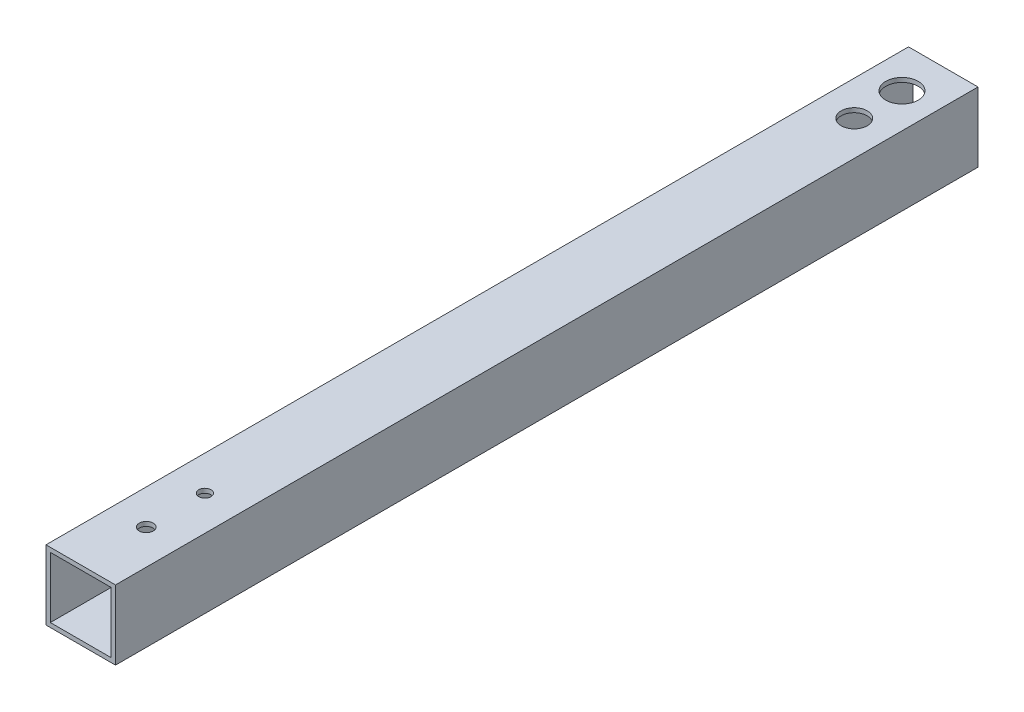
SolidWorks part; units mm, degrees
ref_plane "Front Plane" through (0, 0, 0) normal (0, 0, 1) x (1, 0, 0)
ref_plane "Top Plane" through (0, 0, 0) normal (0, 1, 0) x (1, 0, 0)
ref_plane "Right Plane" through (0, 0, 0) normal (1, 0, 0) x (0, 0, -1)
sketch "Sketch1" plane through (0, 0, 0) normal (0, 0, 1) x (1, 0, 0)
  line L1 (-8, -8) -> (8, -8)
  line L2 (-8, -8) -> (-8, 8)
  line L3 (-8, 8) -> (8, 8)
  line L4 (8, -8) -> (8, 8)
  line L5 (-8, -8) -> (8, 8) construction
  line L6 (-8, 8) -> (8, -8) construction
  line L7 (-7, -7) -> (7, -7)
  line L8 (-7, -7) -> (-7, 7)
  line L9 (-7, 7) -> (7, 7)
  line L10 (7, -7) -> (7, 7)
  line L11 (-7, -7) -> (7, 7) construction
  line L12 (-7, 7) -> (7, -7) construction
  point P0 (0, 0)
  point P6 (0, 0)
  dimension "D1" = 16
  dimension "D2" = 1
extrude "Boss-Extrude1" add sketch "Sketch1" along normal up to surface (198.5758 mm away)
sketch "Sketch2" plane through (0, 8, 0) normal (0, 1, 0) x (1, 0, 0)
  circle A0 centre (0, -9.5) radius 2 construction
  circle A1 centre (0, -20.5) radius 2.4 construction
  circle A2 centre (0, -9.5) radius 2 construction
  circle A3 centre (0, -20.5) radius 2.4 construction
  circle A4 centre (0, -9.5) radius 3.75
  circle A5 centre (0, -20.5) radius 3
  arc A6 (0, -171.025) -> (0, -168.975) centre (0, -170) ccw construction
  circle A7 centre (0, -183.5) radius 1.4 construction
  arc A8 (0, -171.025) -> (0, -168.975) centre (0, -170) ccw construction
  circle A9 centre (0, -183.5) radius 1.4 construction
  circle A10 centre (0, -170) radius 1.4
  circle A11 centre (0, -183.5) radius 1.6
  dimension "D1" = 7.5
  dimension "D2" = 6
  dimension "D3" = 2.8
  dimension "D4" = 3.2
extrude "Cut-Extrude1" cut sketch "Sketch2" against normal through all
ref_axis "Axis1" through (0, 0, 208.5045) along (0, 0, -1)
